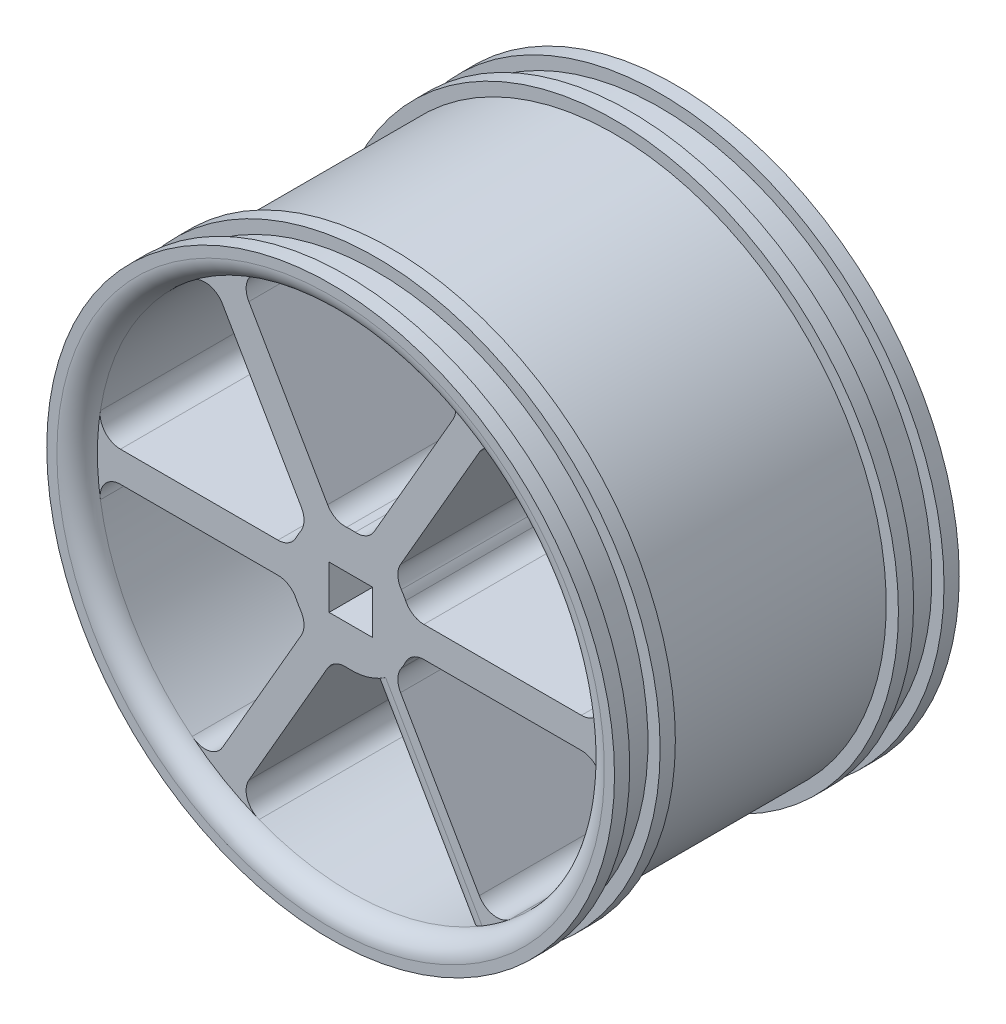
SolidWorks part; units mm, degrees
note: '?' marks a value the reader was unsure of.
ref_plane "Front Plane" through (0, 0, 0) normal (0, 0, 1) x (1, 0, 0)
ref_plane "Top Plane" through (0, 0, 0) normal (0, 1, 0) x (1, 0, 0)
ref_plane "Right Plane" through (0, 0, 0) normal (1, 0, 0) x (0, 0, -1)
ref_plane "Plane1" through (0, 0, 0) normal (0, -1, 0) x (1, 0, 0)
sketch "Sketch1" plane through (0, 0, 0) normal (0, -1, 0) x (1, 0, 0)
  line L2 (25, 0) -> (28, 0)
  line L3 (28, 0) -> (28, 1.5)
  line L4 (28, 1.5) -> (26.8, 1.5)
  line L5 (26.8, 1.5) -> (26.8, 4.5)
  line L6 (26.8, 4.5) -> (28, 4.5)
  line L7 (28, 4.5) -> (28, 6)
  line L8 (28, 6) -> (26.8, 6)
  line L9 (26.8, 6) -> (26.8, 28)
  line L10 (26.8, 28) -> (28, 28)
  line L11 (28, 28) -> (28, 29.5)
  line L12 (28, 29.5) -> (26.8, 29.5)
  line L13 (26.8, 29.5) -> (26.8, 32.5)
  line L14 (26.8, 32.5) -> (28, 32.5)
  line L15 (28, 32.5) -> (28, 34)
  line L16 (0, 34) -> (0, 0) construction
  line L17 (25, 0) -> (25, 32)
  line L19 (0, 0) -> (25, 0) construction
  line L20 (27, 34) -> (28, 34)
  arc A0 (25, 32) -> (27, 34) centre (27, 32) cw
  dimension "D5" = 2
  dimension "D1" = 1.5
  dimension "D2" = 1.2
  dimension "D3" = 3
  dimension "D4" = 25
  dimension "D6" = 32
  dimension "D7" = 3
  dimension "D8" = 1.2
  dimension "D9" = 1.5
  dimension "D10" = 22
  dimension "D11" = 3
  dimension "D12" = 1.5
  dimension "D13" = 25
revolve "Revolve1" add sketch "Sketch1" angle 360 about L16
sketch "Sketch2" plane through (0, 0, 0) normal (0, 0, 1) x (1, 0, 0)
  line L0 (25, 0) -> (0, 0) construction
  line L1 (25, 1.5) -> (0, 1.5)
  line L2 (25, 1.5) -> (25, -1.5)
  line L3 (0, 1.5) -> (0, -1.5)
  line L4 (25, -1.5) -> (0, -1.5)
  line L5 (25, 1.5) -> (0, -1.5) construction
  line L6 (0, 1.5) -> (25, -1.5) construction
  circle A0 centre (0, 0) radius 25 construction
  circle A1 centre (0, 0) radius 25 construction
  point P3 (25, 0)
  point P6 (12.5, 0)
  dimension "D1" = 25
  dimension "D2" = 3
extrude "Boss-Extrude1" add sketch "Sketch2" along normal blind 32
pattern_circular "CirPattern1" count 6 over 360 about axis through (0, 0, 0) along (0, 0, 1) of "Boss-Extrude1"
sketch "Sketch5" plane through (0, 0, 0) normal (0, 0, 1) x (1, 0, 0)
  circle A0 centre (0, 0) radius 6
  dimension "D1" = 12
extrude "Boss-Extrude2" add sketch "Sketch5" along normal blind 32
sketch "Sketch6" plane through (0, 0, 0) normal (0, 0, 1) x (1, 0, 0)
  line L1 (-2.15, 2.15) -> (2.15, 2.15)
  line L2 (-2.15, 2.15) -> (-2.15, -2.15)
  line L3 (-2.15, -2.15) -> (2.15, -2.15)
  line L4 (2.15, 2.15) -> (2.15, -2.15)
  line L5 (-2.15, 2.15) -> (2.15, -2.15) construction
  line L6 (-2.15, -2.15) -> (2.15, 2.15) construction
  point P0 (0, 0)
  dimension "D1" = 4.3
extrude "AxleHole" cut sketch "Sketch6" along normal through all
fillet "Fillet1" radius 2 22 edges at (-24.955, -1.5, 16) (-13.7765, -20.8616, 16) (-11.1784, -22.3616, 16) (13.7765, 20.8616, 16) (13.7765, -20.8616, 16) (5.8095, 1.5, 16) (4.2038, 4.2812, 16) (5.8095, -1.5, 16) (4.2038, -4.2812, 16) (1.6057, 5.7812, 16) (-1.6057, 5.7812, 16) (-4.2038, 4.2812, 16) (-5.8095, 1.5, 16) (-5.8095, -1.5, 16) (-4.2038, -4.2812, 16) (-1.6057, -5.7812, 16) (24.955, 1.5, 16) (24.955, -1.5, 16) (11.1784, 22.3616, 16) (-11.1784, 22.3616, 16) (-13.7765, 20.8616, 16) (-24.955, 1.5, 16)
ref_axis "Axis1" through (0, 0, 47.2787) along (0, 0, -1)?
